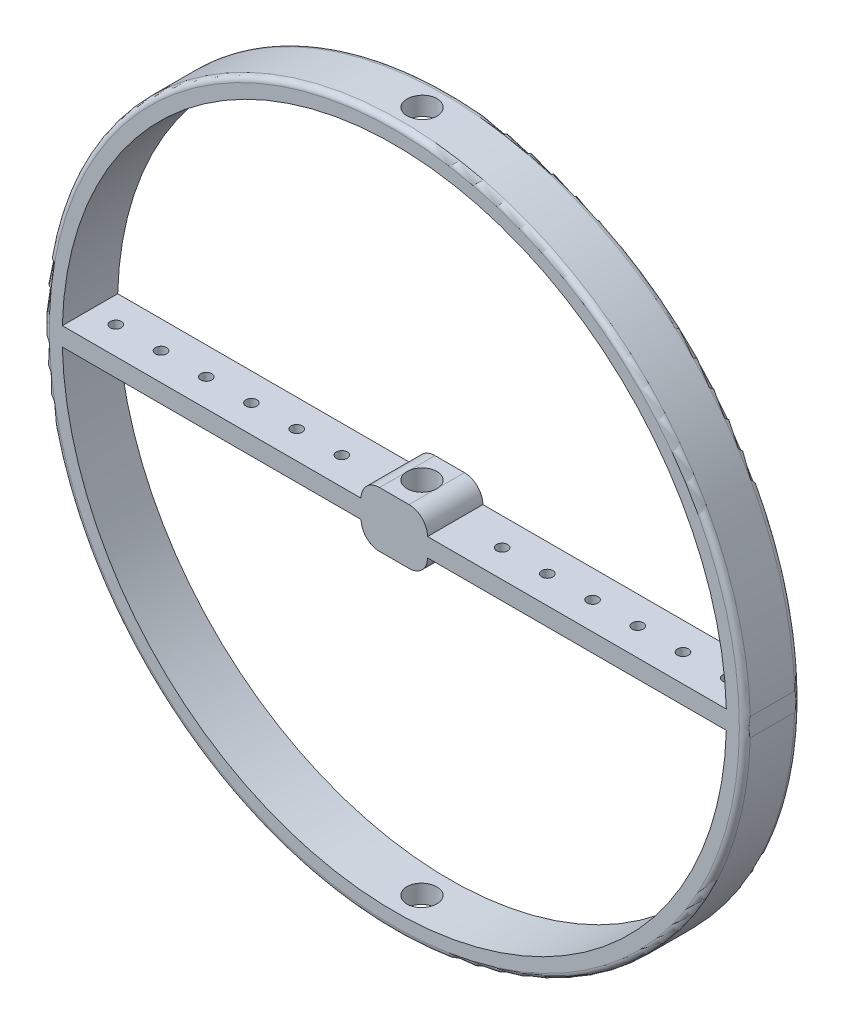
SolidWorks part; units mm, degrees
ref_plane "Front Plane" through (0, 0, 0) normal (0, 0, 1) x (1, 0, 0)
ref_plane "Top Plane" through (0, 0, 0) normal (0, 1, 0) x (1, 0, 0)
ref_plane "Right Plane" through (0, 0, 0) normal (1, 0, 0) x (0, 0, -1)
sketch "Sketch1" plane through (0, 0, 0) normal (0, 0, 1) x (1, 0, 0)
  line L0 (0, 95) -> (0, -95) construction
  line L1 (-95, 0) -> (95, 0) construction
  line L3 (-94.9671, -2.5) -> (94.9671, -2.5)
  line L4 (-94.9671, -2.5) -> (-94.9671, 2.5)
  line L5 (-94.9671, 2.5) -> (94.9671, 2.5)
  line L6 (94.9671, -2.5) -> (94.9671, 2.5)
  line L7 (-94.9671, -2.5) -> (94.9671, 2.5) construction
  line L8 (-94.9671, 2.5) -> (94.9671, -2.5) construction
  line L9 (-9, -7.5) -> (9, -7.5)
  line L10 (-9, -7.5) -> (-9, 7.5)
  line L11 (-9, 7.5) -> (9, 7.5)
  line L12 (9, -7.5) -> (9, 7.5)
  line L13 (-9, -7.5) -> (9, 7.5) construction
  line L14 (-9, 7.5) -> (9, -7.5) construction
  circle A0 centre (0, 0) radius 95
  circle A1 centre (0, 0) radius 90
  dimension "D1" = 15
  dimension "D2" = 5
  dimension "D3" = 18
extrude "Boss-Extrude1" add sketch "Sketch1" along normal blind 15 contours A1 L5 A0 | A1 L3 A0 | A1 L5 L4 L3 | L5 A1 L3 L10 | L3 A1 L5 L12 | A1 L3 L6 L5 | L3 L12 L5 L10 | L5 L12 L11 L10 | L9 L12 L3 L10
sketch "Sketch2" plane through (0, 2.5, 0) normal (0, 1, 0) x (1, 0, 0)
  line L0 (-94.9671, -7.5) -> (94.9671, -7.5) construction
  line L1 (-94.9671, -15) -> (-94.9671, 0) construction
  line L2 (94.9671, -15) -> (94.9671, 0) construction
  line L3 (-89.9653, -15) -> (-89.9653, 0) construction
  circle A0 centre (-82.9653, -7.5) radius 1.5
  dimension "D1" = 7
extrude "Cut-Extrude1" cut sketch "Sketch2" against normal blind 20 contours A0
sketch "Sketch3" plane through (0, 2.5, 0) normal (0, 1, 0) x (1, 0, 0)
  line L2 (89.9653, -15) -> (89.9653, 0) construction
  line L3 (82.9653, -7.5) -> (147.8479, -7.5) construction
  circle A0 centre (82.9653, -7.5) radius 1.5
  dimension "D1" = 7
extrude "Cut-Extrude2" cut sketch "Sketch3" against normal blind 15
sketch "Sketch4" plane through (0, 7.5, 0) normal (0, 1, 0) x (1, 0, 0)
  line L0 (0, 0) -> (0, -15) construction
  line L1 (-94.9671, -15) -> (94.9671, -15) construction
  line L2 (-9, -7.5) -> (9, -7.5) construction
  line L3 (-9, -15) -> (-9, 0) construction
  line L4 (9, -15) -> (9, 0) construction
  circle A0 centre (0, -7.5) radius 4.05
  dimension "D1" = 8.1
extrude "Cut-Extrude3" cut sketch "Sketch4" against normal blind 330 and the other way blind 290 contours A0
sketch "Sketch5" plane through (0, 2.5, 0) normal (0, 1, 0) x (1, 0, 0)
  line L0 (82.9653, -7.5) -> (47.9632, -7.5) construction
  line L1 (-82.9653, -7.5) -> (-47.9632, -7.5) construction
pattern_linear "LPattern3" count 6 spacing 12.25 along (-1, 0, 0) of "Cut-Extrude2"
pattern_linear "LPattern4" count 6 spacing 12.25 along (1, 0, 0) of "Cut-Extrude1"
fillet "Fillet1" radius 5 3 edges at (-9, 5, 15) (-9, 5, 0) (-9, 7.5, 7.5)
fillet "Fillet2" radius 5 3 edges at (9, 5, 15) (9, 5, 0) (9, 7.5, 7.5)
fillet "Fillet3" radius 5 3 edges at (9, -5, 0) (9, -7.5, 7.5) (9, -5, 15)
fillet "Fillet4" radius 5 3 edges at (-9, -5, 0) (-9, -7.5, 7.5) (-9, -5, 15)
fillet "Fillet5" radius 1.5 4 edges at (0, -95, 15) (94.9671, 0, 15) (0, 95, 15) (-94.9671, 0, 15)
fillet "Fillet6" radius 1.5 4 edges at (-94.9671, 0, 0) (0, 95, 0) (94.9671, 0, 0) (0, -95, 0)
